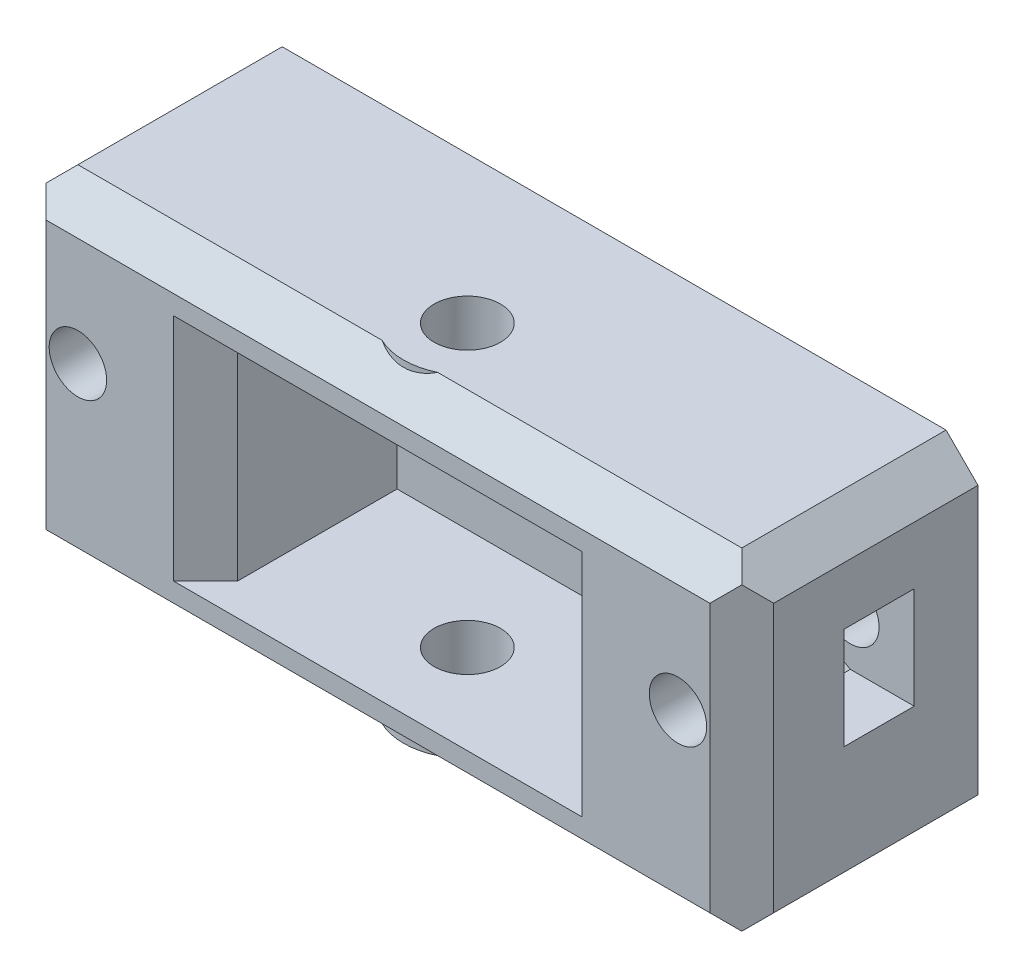
SolidWorks part; units mm, degrees
ref_plane "Plan de face" through (0, 0, 0) normal (0, 0, 1) x (1, 0, 0)
ref_plane "Plan de dessus" through (0, 0, 0) normal (0, 1, 0) x (1, 0, 0)
ref_plane "Plan de droite" through (0, 0, 0) normal (1, 0, 0) x (0, 0, -1)
sketch "Esquisse1" plane through (0, 0, 0) normal (0, 0, 1) x (1, 0, 0)
  line L1 (0, 0) -> (57, 0)
  line L2 (0, 0) -> (0, -26)
  line L3 (0, -26) -> (57, -26)
  line L4 (57, 0) -> (57, -26)
  line L5 (37.5, -6) -> (32, -6)
  line L6 (37.5, -6) -> (37.5, -16)
  line L7 (37.5, -16) -> (32, -16)
  line L8 (32, -6) -> (32, -16)
  line L9 (25, -6) -> (19.5, -6)
  line L10 (25, -6) -> (25, -16)
  line L11 (25, -16) -> (19.5, -16)
  line L12 (19.5, -6) -> (19.5, -16)
  circle A0 centre (5, -11) radius 2.25
  circle A1 centre (52, -11) radius 2.25
  point P17 (34.75, -6)
  point P18 (28.5, 0)
  dimension "D3" = 4.5
  dimension "D4" = 4.5
  dimension "D7" = 11
  dimension "D1" = 26
  dimension "D2" = 57
  dimension "D5" = 5
  dimension "D6" = 5
  dimension "D8" = 11
  dimension "D9" = 5.5
  dimension "D10" = 5.5
  dimension "D11" = 10
  dimension "D12" = 10
  dimension "D13" = 6
  dimension "D14" = 6
  dimension "D15" = 3.5
  dimension "D16" = 3.5
extrude "Boss.-Extru.2" add sketch "Esquisse1" along normal blind 3.5
ref_plane "Plan1" through (28.5, 0, 0) normal (1, 0, 0) x (0, 0, -1)
sketch "Esquisse6" plane through (0, 0, 3.5) normal (0, 0, 1) x (1, 0, 0)
  line L0 (15, 0) -> (15, -26)
  line L1 (57, 0) -> (0, 0) construction
  line L2 (0, -26) -> (57, -26) construction
  line L3 (15, -26) -> (42, -26)
  line L4 (42, -26) -> (42, 0)
  line L5 (42, 0) -> (57, 0)
  line L6 (57, 0) -> (57, -26)
  line L7 (57, -26) -> (42, -26)
  line L8 (15, -26) -> (0, -26)
  line L9 (0, -26) -> (0, 0)
  line L10 (0, 0) -> (15, 0)
  line L11 (15, -22) -> (42, -22)
  line L13 (0, 0) -> (57, 0)
  line L14 (0, 0) -> (0, -4)
  line L15 (0, -4) -> (57, -4)
  line L16 (57, 0) -> (57, -4)
  line L17 (0, -4) -> (57, -4)
  line L18 (0, -4) -> (0, 0)
  line L19 (0, 0) -> (57, 0)
  line L20 (57, -4) -> (57, 0)
  circle M9 centre (5, -11) radius 2.25
  line M10 (0, 0) -> (0, -26)
  line M11 (0, -26) -> (57, -26)
  line M12 (57, -26) -> (57, 0)
  line M13 (57, 0) -> (0, 0)
  circle M14 centre (52, -11) radius 2.25
  line M15 (32, -6) -> (37.5, -6)
  line M19 (19.5, -6) -> (25, -6)
  dimension "D1" = 15
  dimension "D2" = 15
  dimension "D3" = 4
  dimension "D4" = 18
  dimension "D5" = 4
  dimension "D6" = 26
extrude "Boss.-Extru.8" add sketch "Esquisse6" along normal blind 15 and the other way up to surface (3.5 mm away) contours L15 L9 L0 M11 M9 | L11 L0 L4 M11 | L15 L4 M11 M12 M14 | L4 L15 L6 M13 | L0 L15 L4 M19 M15 M13 | L15 L0 M10 M13 region at (28.5, -24, 3.5) region at (7.6266, -15.2025, 3.5) region at (7.5, -2, 3.5) region at (28.5, -2, 3.5) region at (49.3734, -15.2025, 3.5) region at (49.5, -2, 3.5) other way up to face at (34.75, -11, 0)
sketch "Esquisse7" plane through (0, 0, 0) normal (0, 1, 0) x (1, 0, 0)
  line L0 (15, -3.5) -> (42, -3.5) construction
  line L1 (28.5, -10.175) -> (28.5, 10.175) construction
  circle A0 centre (28.5, -11.5) radius 2.6
  point P4 (28.5, -3.5)
  dimension "D1" = 5.2
  dimension "D2" = 8
  dimension "D3" = 0
extrude "Enlèv. mat.-Extru.1" cut sketch "Esquisse7" against normal blind 30
sketch "Esquisse8" plane through (0, 0, 0) normal (0, 0, -1) x (-1, 0, 0)
  line L0 (-57, -26) -> (-57, 0) construction
  line L1 (-48.55, -12.9919) -> (-48.55, -9.0081)
  line L2 (-48.55, -9.0081) -> (-52, -7.0163)
  line L3 (-52, -7.0163) -> (-55.45, -9.0081)
  line L4 (-55.45, -9.0081) -> (-55.45, -12.9919)
  line L5 (-55.45, -12.9919) -> (-52, -14.9837)
  line L6 (-52, -14.9837) -> (-48.55, -12.9919)
  line L7 (-52, -7.0163) -> (-57, -7.0163)
  line L8 (-57, -7.0163) -> (-57, -14.9837)
  line L9 (-57, -14.9837) -> (-52, -14.9837)
  circle A0 centre (-52, -11) radius 3.45 construction
  line M7 (-57, 0) -> (-57, -26)
  circle M12 centre (-52, -11) radius 2.25
  dimension "D1" = 180
  dimension "D2" = 6.9
  dimension "D3" = 90
  dimension "D4" = 90
extrude "Enlèv. mat.-Extru.2" cut sketch "Esquisse8" against normal blind 5.5 from offset 5 contours L9 L5 L4 L3 L7 M7 | L5 L6 L1 L2 L3 L4 M12 region at (50.3277, -13.8965, 0) region at (55.5368, -11, 0) offset against normal yes
mirror "Symétrie1" about plane through (28.5, 0, 0) normal (1, 0, 0) of "Enlèv. mat.-Extru.2"
chamfer "Chanfrein2" distance 2.5 angle 45 2 edges at (57, -13, 18.5) (0, -13, 18.5)
chamfer "Chanfrein3" distance 2.5 angle 45 8 edges at (57, -26, 8) (57, 0, 8) (0, 0, 8) (0, -26, 8) (42, -13, 18.5) (15, -13, 18.5) (28.5, -26, 18.5) (28.5, 0, 18.5)
sketch "Esquisse10" plane through (0, 0, 0) normal (0, 1, 0) x (1, 0, 0)
  circle A0 centre (28.5, -11.5) radius 5
  circle A1 centre (28.5, -11.5) radius 2.75
  dimension "D1" = 10
extrude "Boss.-Extru.9" add sketch "Esquisse10" against normal up to next (4 mm away)
ref_plane "Plan2" through (0, -13, 0) normal (0, 1, 0) x (1, 0, 0)
mirror "Symétrie2" about plane through (0, -13, 0) normal (0, 1, 0) of "Boss.-Extru.9"
